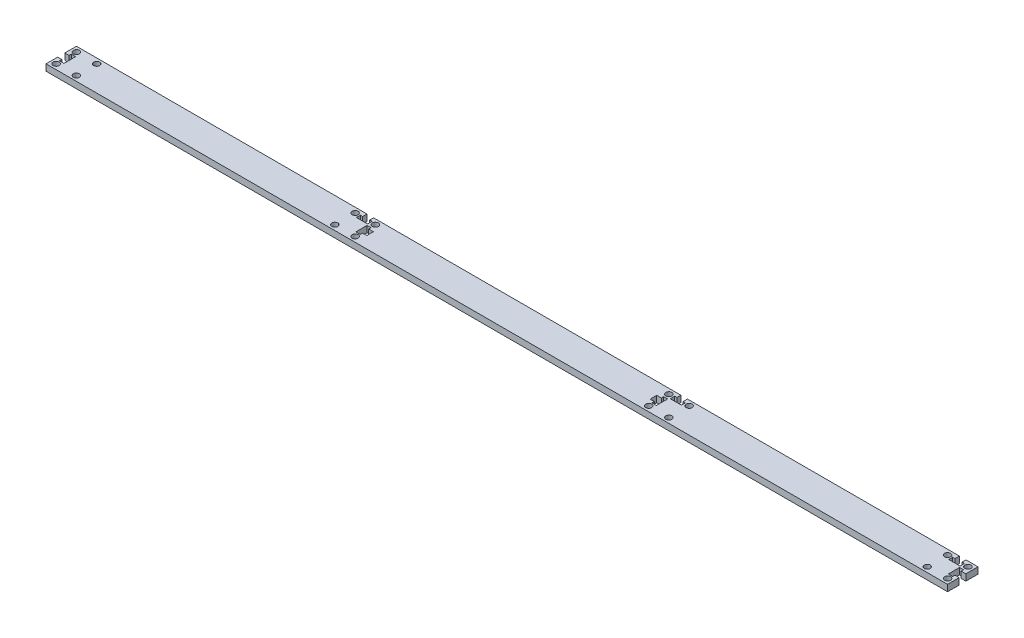
SolidWorks part; units mm, degrees
ref_plane "Front Plane" through (0, 0, 0) normal (0, 0, 1) x (1, 0, 0)
ref_plane "Top Plane" through (0, 0, 0) normal (0, 1, 0) x (1, 0, 0)
ref_plane "Right Plane" through (0, 0, 0) normal (1, 0, 0) x (0, 0, -1)
sketch "Sketch1" plane through (0, 0, 0) normal (0, 1, 0) x (1, 0, 0)
  line L0 (152.4, 7.5) -> (144.9, 7.5)
  line L1 (0, 0) -> (152.4, 0)
  line L2 (0, 0) -> (0, 15)
  line L3 (0, 15) -> (152.4, 15)
  line L4 (152.4, 0) -> (152.4, 15)
  line L5 (0, 7.5) -> (7.5, 7.5)
  line L6 (7.5, 7.5) -> (7.5, 12.5)
  line L7 (7.5, 12.5) -> (2.5, 12.5)
  line L8 (7.5, 12.5) -> (12.5, 12.5)
  line L9 (7.5, 7.5) -> (7.5, 2.5)
  line L10 (7.5, 2.5) -> (2.5, 2.5)
  line L11 (7.5, 2.5) -> (12.5, 2.5)
  line L12 (76.2, 0) -> (76.2, 15)
  line L13 (152.4, 0) -> (152.4, 15)
  line L14 (152.4, 0) -> (292.1, 0)
  line L15 (152.4, 15) -> (292.1, 15)
  line L16 (222.25, 0) -> (222.25, 15)
  line L17 (292.1, 0) -> (292.1, 15)
  line L18 (444.5, 15) -> (292.1, 15)
  line L19 (292.1, 0) -> (292.1, 15)
  line L20 (444.5, 0) -> (292.1, 0)
  line L21 (444.5, 0) -> (444.5, 15)
  circle A0 centre (2.5, 2.5) radius 1.5
  circle A1 centre (2.5, 12.5) radius 1.5
  circle A2 centre (12.5, 12.5) radius 1.5
  circle A3 centre (12.5, 2.5) radius 1.5
  circle A4 centre (149.9, 12.5) radius 1.5
  circle A5 centre (139.9, 12.5) radius 1.5
  circle A6 centre (149.9, 2.5) radius 1.5
  circle A7 centre (139.9, 2.5) radius 1.5
  circle A8 centre (432, 12.5) radius 1.5
  circle A9 centre (442, 12.5) radius 1.5
  circle A10 centre (442, 2.5) radius 1.5
  circle A11 centre (432, 2.5) radius 1.5
  circle A12 centre (294.6, 12.5) radius 1.5
  circle A13 centre (304.6, 12.5) radius 1.5
  circle A14 centre (304.6, 2.5) radius 1.5
  circle A15 centre (294.6, 2.5) radius 1.5
  dimension "D11" = 69.85
  dimension "D1" = 15
  dimension "D2" = 152.4
  dimension "D3" = 7.5
  dimension "D4" = 7.5
  dimension "D5" = 5
  dimension "D6" = 5
  dimension "D7" = 5
  dimension "D8" = 5
  dimension "D9" = 5
  dimension "D10" = 5
extrude "Boss-Extrude1" add sketch "Sketch1" along normal blind 3.175 contours A3 A0 L2 L1 L12 L3 A1 A2 | L12 L1 L4 L3 A6 A4 A5 A7 | L14 L16 L15 L4 | L14 L17 L15 L16 | L20 L21 L18 L17 A15 A14 A13 A12 A10 A8 A9 A11 region at (38.8762, 0, -7.5) region at (113.5238, 0, -7.5) region at (187.325, 0, -7.5) region at (257.175, 0, -7.5) region at (368.3, 0, -7.5)
sketch "Sketch4" plane through (0, 3.175, 0) normal (0, 1, 0) x (1, 0, 0)
  line L0 (444.5, 7.5) -> (432.4339, 7.5)
  line L1 (444.5, 0) -> (444.5, 15) construction
  line L2 (0, 15) -> (444.5, 15) construction
  line L3 (222.25, 15) -> (222.25, 0)
  line L4 (0, 0) -> (444.5, 0) construction
  line L5 (444.5, 9) -> (442.2, 9)
  line L6 (442.2, 9) -> (442.2, 10.15)
  line L7 (442.2, 10.15) -> (440.5, 10.15)
  line L8 (440.5, 10.15) -> (440.5, 7.5)
  line L9 (444.5, 9.25) -> (442.45, 9.25)
  line L10 (442.45, 9.25) -> (442.45, 10.4)
  line L11 (442.45, 10.4) -> (440.25, 10.4)
  line L12 (440.25, 10.4) -> (440.25, 7.5)
  line L13 (444.5, 5.75) -> (442.45, 5.75)
  line L14 (442.45, 5.75) -> (442.45, 4.6)
  line L15 (442.45, 4.6) -> (440.25, 4.6)
  line L16 (440.25, 4.6) -> (440.25, 7.5)
  line L17 (0, 9.25) -> (2.05, 9.25)
  line L18 (2.05, 9.25) -> (2.05, 10.4)
  line L19 (0, 5.75) -> (2.05, 5.75)
  line L20 (2.05, 5.75) -> (2.05, 4.6)
  line L21 (2.05, 4.6) -> (4.25, 4.6)
  line L22 (4.25, 4.6) -> (4.25, 7.5)
  line L23 (4.25, 10.4) -> (4.25, 7.5)
  line L24 (2.05, 10.4) -> (4.25, 10.4)
  line L25 (0, 9.25) -> (0, 5.75)
  line L26 (444.5, 9.25) -> (444.5, 5.75)
  line M20 (0, 15) -> (0, 0)
  line M22 (444.5, 0) -> (444.5, 15)
  dimension "D1" = 1.5
  dimension "D2" = 1.15
  dimension "D3" = 1.7
  dimension "D4" = 2.65
  dimension "D5" = 2.3
  dimension "D6" = 0.25
extrude "Cut-Extrude2" cut sketch "Sketch4" against normal blind 10 contours L16 L15 L14 L13 L0 M22 | L7 L8 L0 L5 L6 M22 | L24 L18 L17 L19 L20 L21 L22 L23 M20 region at (442.1148, 3.175, -6.257) region at (442.2174, 3.175, -8.5756) region at (2.3852, 3.175, -7.5)
sketch "Sketch6" plane through (440.5, 0, 0) normal (1, 0, 0) x (0, 0, -1)
  line L0 (10.15, 0) -> (7.5, 0) construction
  line L5 (7.5, 3.175) -> (10.15, 3.175)
  line L6 (7.5, 3.175) -> (7.5, 0)
  line L7 (7.5, 0) -> (10.15, 0)
  line L8 (10.15, 3.175) -> (10.15, 0)
extrude "Cut-Extrude3" cut sketch "Sketch6" against normal blind 0.25
sketch "Sketch7" plane through (0, 3.175, 0) normal (0, 1, 0) x (1, 0, 0)
  line L0 (440.25, 4.6) -> (440.25, 10.15)
  line L1 (440.25, 10.15) -> (442.2, 10.15)
  line L2 (442.2, 10.15) -> (442.2, 9)
  line L3 (442.2, 9) -> (444.5, 9)
  line L4 (444.5, 9) -> (444.5, 5.75)
  line L5 (444.5, 5.75) -> (442.45, 5.75)
  line L6 (444.5, 5.75) -> (442.45, 5.75) construction
  line L7 (442.45, 5.75) -> (442.45, 4.6)
  line L8 (442.45, 5.75) -> (442.45, 4.6) construction
  line L9 (442.45, 4.6) -> (440.25, 4.6) construction
  line L10 (442.45, 4.6) -> (440.25, 4.6)
  line L11 (368.3, 15) -> (368.3, 0)
  line L12 (0, 15) -> (444.5, 15) construction
  line L13 (0, 0) -> (444.5, 0) construction
  line L30 (439.75, 13.1) -> (439.75, 10.9)
  line L31 (439.75, 10.9) -> (434.2, 10.9)
  line L32 (434.2, 10.9) -> (434.2, 12.85)
  line L33 (434.2, 12.85) -> (435.35, 12.85)
  line L34 (435.35, 12.85) -> (435.35, 15.15)
  line L35 (435.35, 15.15) -> (438.6, 15.15)
  line L36 (438.6, 15.15) -> (438.6, 13.1)
  line L37 (438.6, 13.1) -> (439.75, 13.1)
  line L38 (431.25, 10.4) -> (433.45, 10.4) [skipped]
  line L39 (433.45, 10.4) -> (433.45, 4.85) [skipped]
  line L40 (433.45, 4.85) -> (431.5, 4.85) [skipped]
  line L41 (431.5, 4.85) -> (431.5, 6) [skipped]
  line L42 (431.5, 6) -> (429.2, 6) [skipped]
  line L43 (429.2, 6) -> (429.2, 9.25) [skipped]
  line L44 (429.2, 9.25) -> (431.25, 9.25) [skipped]
  line L45 (431.25, 9.25) -> (431.25, 10.4) [skipped]
  line L46 (433.95, 1.9) -> (433.95, 4.1) [skipped]
  line L47 (433.95, 4.1) -> (439.5, 4.1) [skipped]
  line L48 (439.5, 4.1) -> (439.5, 2.15) [skipped]
  line L49 (439.5, 2.15) -> (438.35, 2.15) [skipped]
  line L50 (438.35, 2.15) -> (438.35, -0.15) [skipped]
  line L51 (438.35, -0.15) -> (435.1, -0.15) [skipped]
  line L52 (435.1, -0.15) -> (435.1, 1.9) [skipped]
  line L53 (435.1, 1.9) -> (433.95, 1.9) [skipped]
  line L54 (298, 13.1) -> (296.85, 13.1)
  line L55 (298, 15.15) -> (298, 13.1)
  line L56 (301.25, 15.15) -> (298, 15.15)
  line L57 (301.25, 12.85) -> (301.25, 15.15)
  line L58 (302.4, 12.85) -> (301.25, 12.85)
  line L59 (302.4, 10.9) -> (302.4, 12.85)
  line L60 (296.85, 10.9) -> (302.4, 10.9)
  line L61 (296.85, 13.1) -> (296.85, 10.9)
  line L62 (294.15, 4.6) -> (296.35, 4.6)
  line L63 (294.15, 5.75) -> (294.15, 4.6)
  line L64 (292.1, 5.75) -> (294.15, 5.75)
  line L65 (292.1, 9) -> (292.1, 5.75)
  line L66 (294.4, 9) -> (292.1, 9)
  line L67 (294.4, 10.15) -> (294.4, 9)
  line L68 (296.35, 10.15) -> (294.4, 10.15)
  line L69 (296.35, 4.6) -> (296.35, 10.15)
  line L70 (222.25, 15) -> (222.25, -3.2604)
  line L71 (148.15, 4.6) -> (148.15, 10.15)
  line L72 (148.15, 10.15) -> (150.1, 10.15)
  line L73 (150.1, 10.15) -> (150.1, 9)
  line L74 (150.1, 9) -> (152.4, 9)
  line L75 (152.4, 9) -> (152.4, 5.75)
  line L76 (152.4, 5.75) -> (150.35, 5.75)
  line L77 (150.35, 5.75) -> (150.35, 4.6)
  line L78 (150.35, 4.6) -> (148.15, 4.6)
  line L79 (147.65, 13.1) -> (147.65, 10.9)
  line L80 (147.65, 10.9) -> (142.1, 10.9)
  line L81 (142.1, 10.9) -> (142.1, 12.85)
  line L82 (142.1, 12.85) -> (143.25, 12.85)
  line L83 (143.25, 12.85) -> (143.25, 15.15)
  line L84 (143.25, 15.15) -> (146.5, 15.15)
  line L85 (146.5, 15.15) -> (146.5, 13.1)
  line L86 (146.5, 13.1) -> (147.65, 13.1)
  circle A0 centre (294.6, 12.5) radius 1.5 construction
  line M51 (440.25, 4.6) -> (440.25, 10.15)
  line M52 (440.25, 10.15) -> (442.2, 10.15)
  line M53 (442.2, 10.15) -> (442.2, 9)
  line M54 (442.2, 9) -> (444.5, 9)
  line M56 (444.5, 15) -> (0, 15)
  line M68 (444.5, 5.75) -> (442.45, 5.75)
  line M69 (442.45, 5.75) -> (442.45, 4.6)
  line M70 (442.45, 4.6) -> (440.25, 4.6)
  dimension "D1" = 73.7
  dimension "D2" = 4
extrude "Cut-Extrude4" cut sketch "Sketch7" against normal blind 10 contours L78 L77 L76 L75 L74 L73 L72 L71 | L86 L85 L83 L82 L81 L80 L79 M56 | L62 L69 L68 L67 L66 L65 L64 L63 | L54 L61 L60 L59 L58 L57 L55 M56 | L37 L36 L34 L33 L32 L31 L30 M56 | L4 M54 M53 M52 M51 M70 M69 M68 region at (442.0967, 3.175, -7.341) region at (144.9099, 3.175, -12.684) region at (299.5901, 3.175, -12.684) region at (437.0099, 3.175, -12.684) region at (294.5033, 3.175, -7.341) region at (149.9967, 3.175, -7.341)
